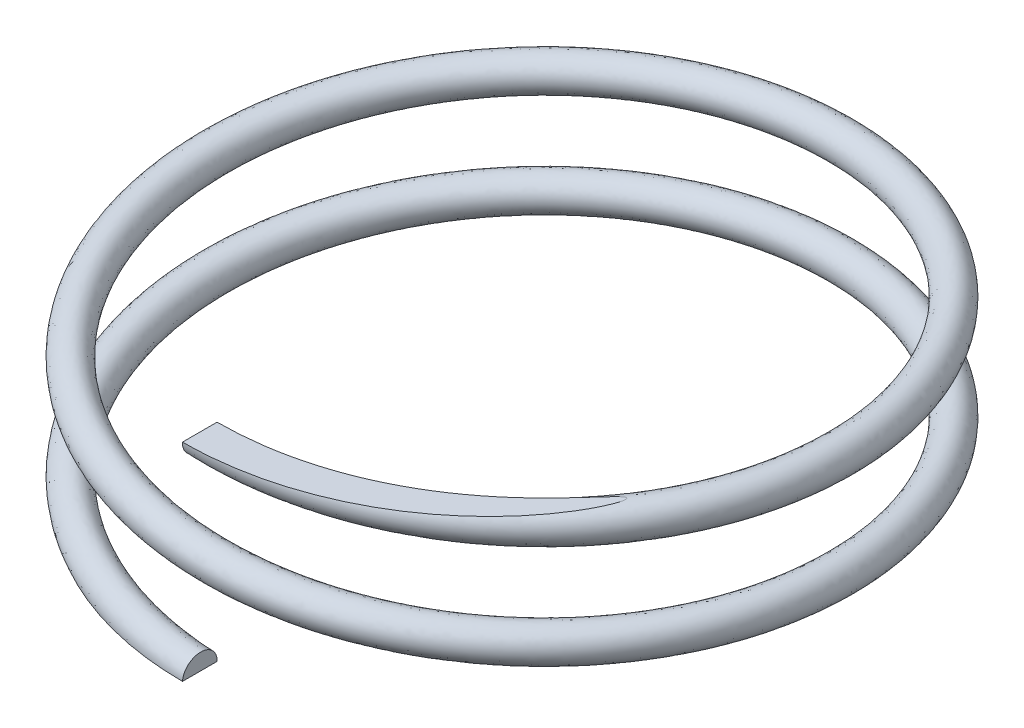
SolidWorks part; units mm, degrees
material "Сталь 3 ГОСТ 535-88"
ref_plane "Спереди" through (0, 0, 0) normal (0, 0, 1) x (1, 0, 0)
ref_plane "Сверху" through (0, 0, 0) normal (0, 1, 0) x (1, 0, 0)
ref_plane "Справа" through (0, 0, 0) normal (1, 0, 0) x (0, 0, -1)
sketch "Эскиз2" plane through (0, 0, 0) normal (0, 1, 0) x (1, 0, 0)
  circle A0 centre (0, 0) radius 45
  dimension "D1" = 90
curve "Спираль1" pitch 15 height 30 radius 45 left hand yes centre (0, 0, 0) axis (0, 1, 0) start towards (0, 0, 1)
ref_plane "Плоскость1" through (0, 0, 45) normal (-0.9986, 0.053, 0) x (0, 0, 1)
sketch "Эскиз3" plane through (0, 0, 45) normal (-0.9986, 0.053, 0) x (0, 0, 1)
  circle A0 centre (0.197, 0) radius 2.5
  dimension "D1" = 5
sweep "По траектории1" add profiles "Эскиз3" path "Спираль1"
sketch "Эскиз4" plane through (0, 0, 0) normal (0, 1, 0) x (1, 0, 0)
  line L1 (-63.7664, 67.7576) -> (70.4263, 67.7576)
  line L2 (-63.7664, 67.7576) -> (-63.7664, -67.7576)
  line L3 (-63.7664, -67.7576) -> (70.4263, -67.7576)
  line L4 (70.4263, 67.7576) -> (70.4263, -67.7576)
  line L5 (3.33, -67.7576) -> (3.33, 67.7576) construction
  line L6 (-63.7664, 0) -> (70.4263, 0) construction
  point P0 (3.33, 0)
extrude "Вырез-Вытянуть1" cut sketch "Эскиз4" against normal through all
ref_plane "Плоскость2" through (0, 30, 0) normal (0, 1, 0) x (1, 0, 0)
sketch "Эскиз5" plane through (0, 30, 0) normal (0, 1, 0) x (1, 0, 0)
  line L4 (70.4263, 67.7576) -> (-63.7664, 67.7576)
  line L5 (-63.7664, 67.7576) -> (-63.7664, -67.7576)
  line L6 (-63.7664, -67.7576) -> (70.4263, -67.7576)
  line L7 (70.4263, -67.7576) -> (70.4263, 67.7576)
  line L8 (70.4263, 67.7576) -> (-63.7664, 67.7576)
  line L9 (-63.7664, 67.7576) -> (-63.7664, -67.7576)
  line L10 (-63.7664, -67.7576) -> (70.4263, -67.7576)
  line L11 (70.4263, -67.7576) -> (70.4263, 67.7576)
  dimension "D1" = 0
extrude "Вырез-Вытянуть2" cut sketch "Эскиз5" along normal through all
